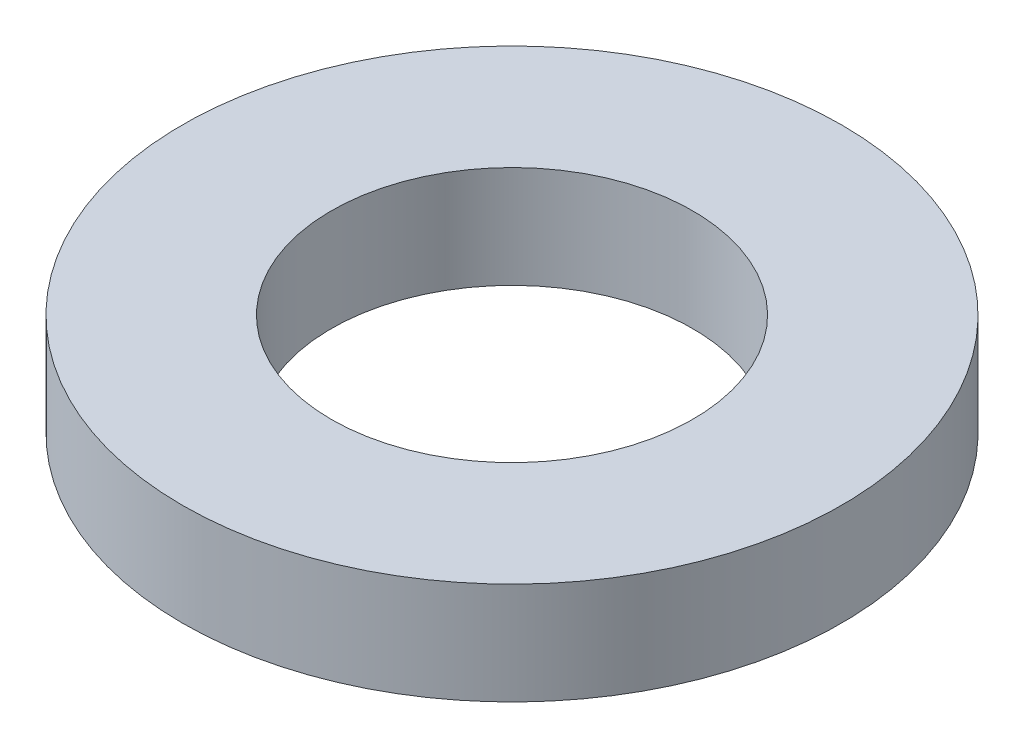
SolidWorks part; units mm, degrees
ref_plane "Front Plane" through (0, 0, 0) normal (0, 0, 1) x (1, 0, 0)
ref_plane "Top Plane" through (0, 0, 0) normal (0, 1, 0) x (1, 0, 0)
ref_plane "Right Plane" through (0, 0, 0) normal (1, 0, 0) x (0, 0, -1)
sketch "Sketch1" plane through (0, 0, 0) normal (0, 1, 0) x (1, 0, 0)
  circle A0 centre (0, 0) radius 77.5
  dimension "FLANGE_OD" = 155
extrude "Boss-Extrude1" add sketch "Sketch1" along normal blind 24
sketch "Sketch2" plane through (0, 0, 0) normal (0, 1, 0) x (1, 0, 0)
  circle A0 centre (0, 0) radius 42.5
  dimension "BORE_D" = 85
extrude "Cut-Extrude1" cut sketch "Sketch2" along normal through all
sketch "Sketch3" plane through (0, 24, 0) normal (0, 1, 0) x (1, 0, 0)
  circle A0 centre (0, 0) radius 33.806 construction
  circle A1 centre (-33.806, 0) radius 2.3184
  dimension "BOLT_D" = 4.6368
  dimension "BOLT_PCD" = 67.612
extrude "Cut-Extrude2" cut sketch "Sketch3" against normal blind 22.4223 rebuild error yes
pattern_circular "CirPattern1" count 6 over 360 rebuild error yes
